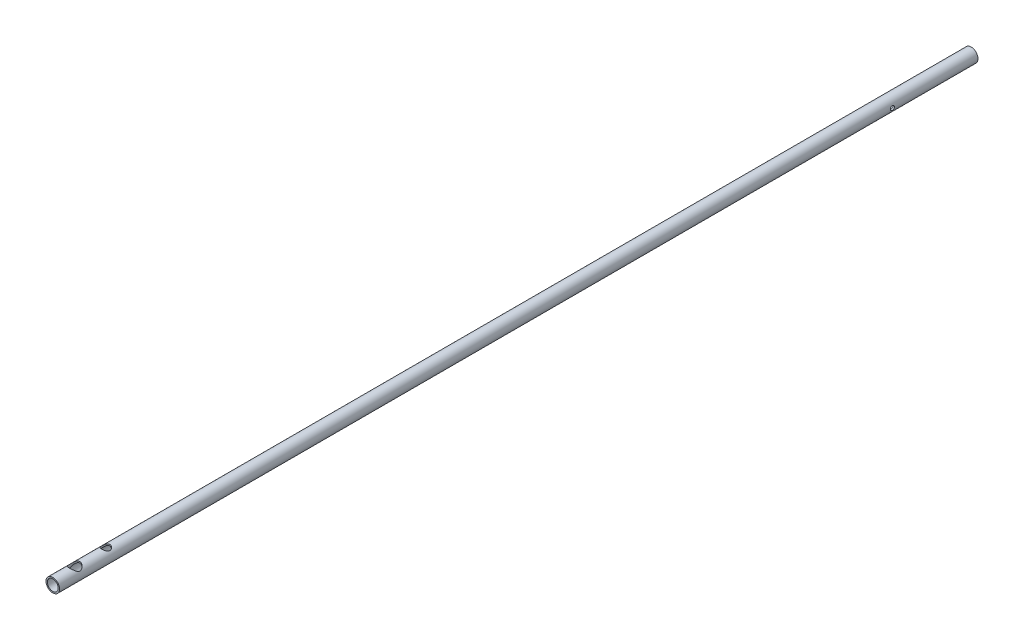
SolidWorks part; units mm, degrees
material "1060 合金"
ref_plane "正面" through (0, 0, 0) normal (0, 0, 1) x (1, 0, 0)
ref_plane "平面" through (0, 0, 0) normal (0, 1, 0) x (1, 0, 0)
ref_plane "右側面" through (0, 0, 0) normal (1, 0, 0) x (0, 0, -1)
sketch "ｽｹｯﾁ1" plane through (0, 0, 0) normal (0, 0, 1) x (1, 0, 0)
  circle A0 centre (0, 0) radius 5
  dimension "D1" = 10
extrude "押し出し-薄板1" add sketch "ｽｹｯﾁ1" along normal blind 676.5 thin thin type one direction reverse wall 1
sketch "ｽｹｯﾁ2" plane through (0, 0, 0) normal (0, 1, 0) x (1, 0, 0)
  line L0 (0, 0) -> (0, 50000) construction
  line L1 (-5, -676.5) -> (5, -676.5) construction
  circle A0 centre (0, -660.5) radius 2
  circle A1 centre (0, -637.5) radius 1.5
  circle A2 centre (0, -660.5) radius 4
  circle A3 centre (0, -637.5) radius 3
  dimension "D1" = 16
  dimension "D2" = 23
  dimension "D3" = 4
  dimension "D4" = 8
  dimension "D5" = 6
  dimension "D6" = 3
extrude "ｶｯﾄ - 押し出し1" cut sketch "ｽｹｯﾁ2" against normal through all both and the other way through all contours L0 A1 | A1 L0 | L0 A0 | A0 L0 region at (0, 0, 660.5) region at (0, 0, 637.5)
extrude "ｶｯﾄ - 押し出し2" cut sketch "ｽｹｯﾁ2<3>" along normal through all contours A2 | A3
sketch "ｽｹｯﾁ2<3>" plane through (0, 0, 0) normal (0, 1, 0) x (1, 0, 0) same geometry as "ｽｹｯﾁ2"
sketch "ｽｹｯﾁ3" plane through (0, 0, 0) normal (1, 0, 0) x (0, 0, -1)
  line L0 (0, 0) -> (50000, 0) construction
  line L1 (0, -5) -> (0, 5) construction
  circle A0 centre (-63, 0) radius 1.5
  circle A1 centre (-63, 0) radius 3
  dimension "D1" = 63
  dimension "D2" = 3
  dimension "D3" = 6
extrude "ｶｯﾄ - 押し出し3" cut sketch "ｽｹｯﾁ3" against normal through all both and the other way through all contours A0
extrude "ｶｯﾄ - 押し出し4" cut sketch "ｽｹｯﾁ3<3>" against normal blind 10 contours A1
sketch "ｽｹｯﾁ3<3>" plane through (0, 0, 0) normal (1, 0, 0) x (0, 0, -1) same geometry as "ｽｹｯﾁ3"
